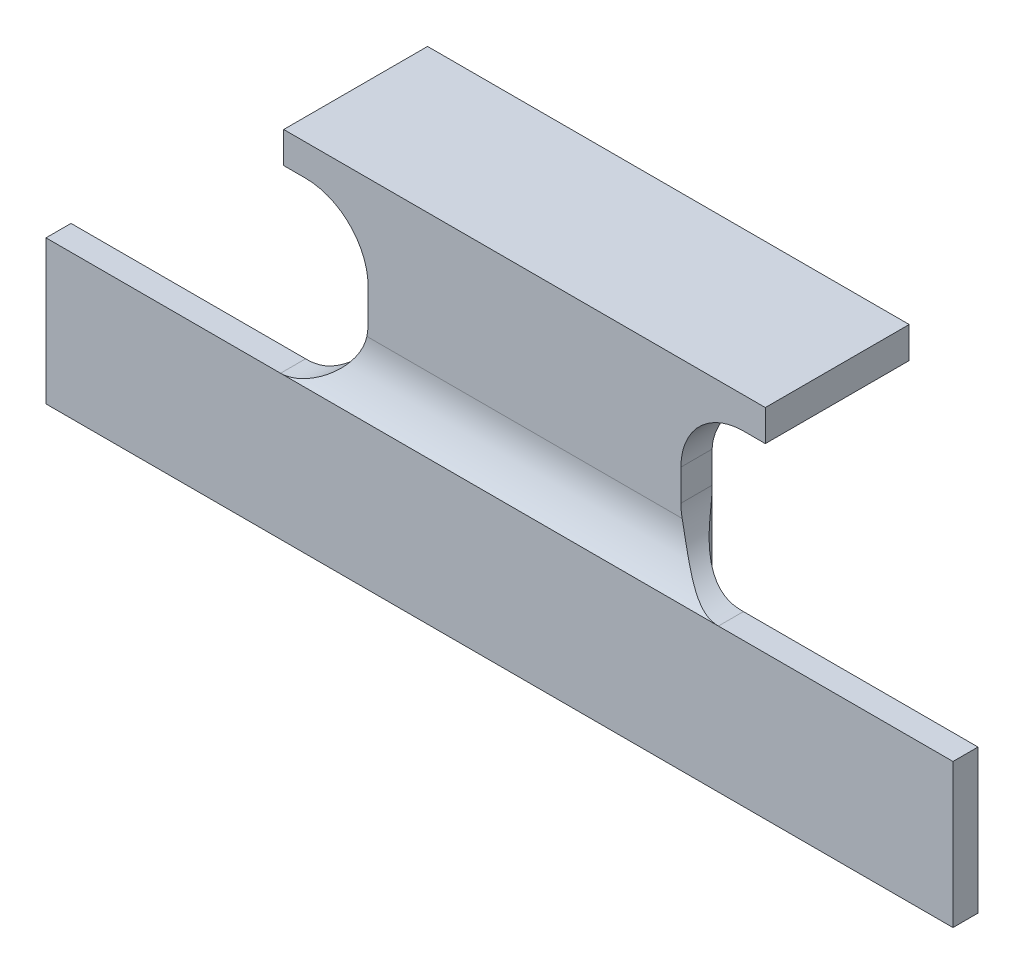
SolidWorks part; units mm, degrees
ref_plane "前视基准面" through (0, 0, 0) normal (0, 0, 1) x (1, 0, 0)
ref_plane "上视基准面" through (0, 0, 0) normal (0, 1, 0) x (1, 0, 0)
ref_plane "右视基准面" through (0, 0, 0) normal (1, 0, 0) x (0, 0, -1)
sketch "草图1" plane through (0, 0, 0) normal (0, 0, 1) x (1, 0, 0)
  line L1 (-72.5, 11.5) -> (72.5, 11.5)
  line L2 (-72.5, 11.5) -> (-72.5, -11.5)
  line L3 (-72.5, -11.5) -> (72.5, -11.5)
  line L4 (72.5, 11.5) -> (72.5, -11.5)
  line L5 (-72.5, 11.5) -> (72.5, -11.5) construction
  line L6 (-72.5, -11.5) -> (72.5, 11.5) construction
  point P0 (0, 0)
  dimension "D1" = 145
  dimension "D2" = 23
extrude "凸台-拉伸1" add sketch "草图1" along normal blind 4
sketch "草图2" plane through (0, 0, 0) normal (0, 1, 0) x (1, 0, 0)
  line L0 (72.5, 0) -> (-72.5, 0) construction
  line L1 (-25, 0) -> (25, 0)
  line L2 (-25, 0) -> (-25, 5)
  line L3 (-25, 5) -> (25, 5)
  line L4 (25, 0) -> (25, 5)
  point P6 (0, 5)
  dimension "D1" = 50
  dimension "D2" = 5
extrude "凸台-拉伸2" add sketch "草图2" along normal blind 36.5 and the other way blind 11.5
sketch "草图3" plane through (0, 36.5, 0) normal (0, 1, 0) x (1, 0, 0)
  line L0 (-25, 0) -> (-72.5, 0) construction
  line L1 (-38.5, 0) -> (38.5, 0)
  line L2 (-38.5, 0) -> (-38.5, 23)
  line L3 (-38.5, 23) -> (38.5, 23)
  line L4 (38.5, 0) -> (38.5, 23)
  point P6 (0, 23)
  dimension "D1" = 77
  dimension "D2" = 23
extrude "凸台-拉伸3" add sketch "草图3" along normal blind 5
fillet "圆角1" radius 10 3 edges at (-25, 36.5, -2.5) (25, 36.5, -2.5) (0, 36.5, -5)
fillet "圆角2" radius 10 2 edges at (-25, 0, 0) (25, 0, 0)
fillet "圆角3" radius 10 3 edges at (25, 11.5, -2.5) (-25, 11.5, -2.5) (0, 11.5, 0)
